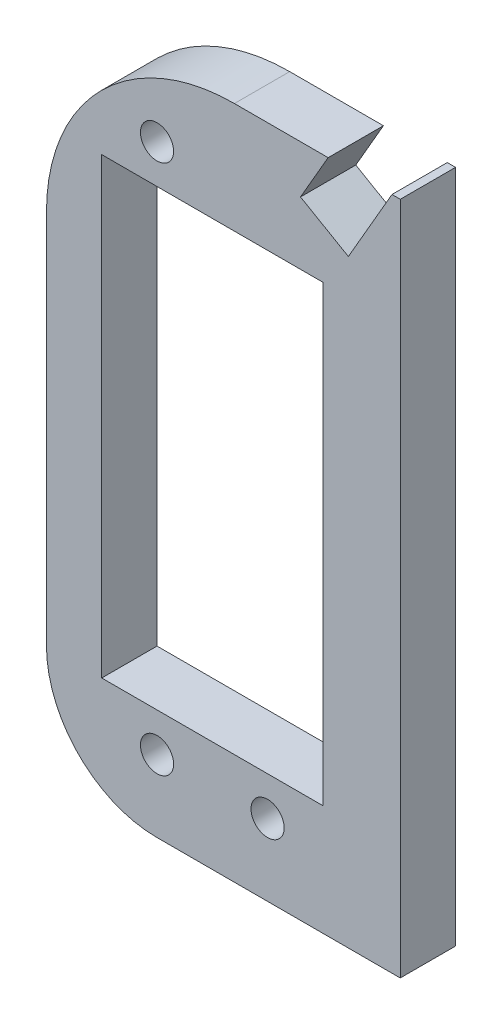
SolidWorks part; units mm, degrees
ref_plane "Plan de face" through (0, 0, 0) normal (0, 0, 1) x (1, 0, 0)
ref_plane "Plan de dessus" through (0, 0, 0) normal (0, 1, 0) x (1, 0, 0)
ref_plane "Plan de droite" through (0, 0, 0) normal (1, 0, 0) x (0, 0, -1)
sketch "Esquisse1" plane through (0, 0, 0) normal (0, 0, 1) x (1, 0, 0)
  line L0 (15, 10) -> (15, 51) construction
  line L1 (0, 0) -> (25, 0)
  line L2 (0, 0) -> (0, 61)
  line L3 (0, 61) -> (15, 61)
  line L4 (31.2508, 61) -> (27.3074, 54.1699)
  line L5 (15, 51) -> (5, 51)
  line L6 (15, 61) -> (25.4773, 61)
  line L7 (25, 10) -> (5, 10)
  line L8 (5, 51) -> (5, 10)
  line L9 (5, 30.5) -> (25, 30.5) construction
  line L10 (25, 10) -> (25, 51)
  line L11 (25, 51) -> (15, 51)
  line L12 (25, 0) -> (32, 0)
  line L13 (32, 0) -> (32, 61)
  line L14 (31.0278, 60.6138) -> (27.2778, 54.1186) construction
  line L15 (27.3074, 54.1699) -> (22.9773, 56.6699)
  line L16 (22.9773, 56.6699) -> (25.4773, 61)
  line L17 (31.2508, 61) -> (32, 61)
  circle A0 centre (10, 54.5) radius 1.5
  circle A1 centre (20, 54.5) radius 1.5 construction
  circle A2 centre (20, 6.5) radius 1.5
  circle A3 centre (10, 6.5) radius 1.5
  dimension "D6" = 3.5
  dimension "D8" = 3
  dimension "D1" = 20
  dimension "D2" = 41
  dimension "D3" = 10
  dimension "D4" = 10
  dimension "D5" = 5
  dimension "D7" = 5
  dimension "D9" = 7
  dimension "D10" = 5
  dimension "D11" = 5
extrude "Boss.-Extru.1" add sketch "Esquisse1" along normal blind 5
fillet "Congé1" radius 17 1 edges at (0, 61, 2.5)
fillet "Congé2" radius 10 1 edges at (0, 0, 2.5)
